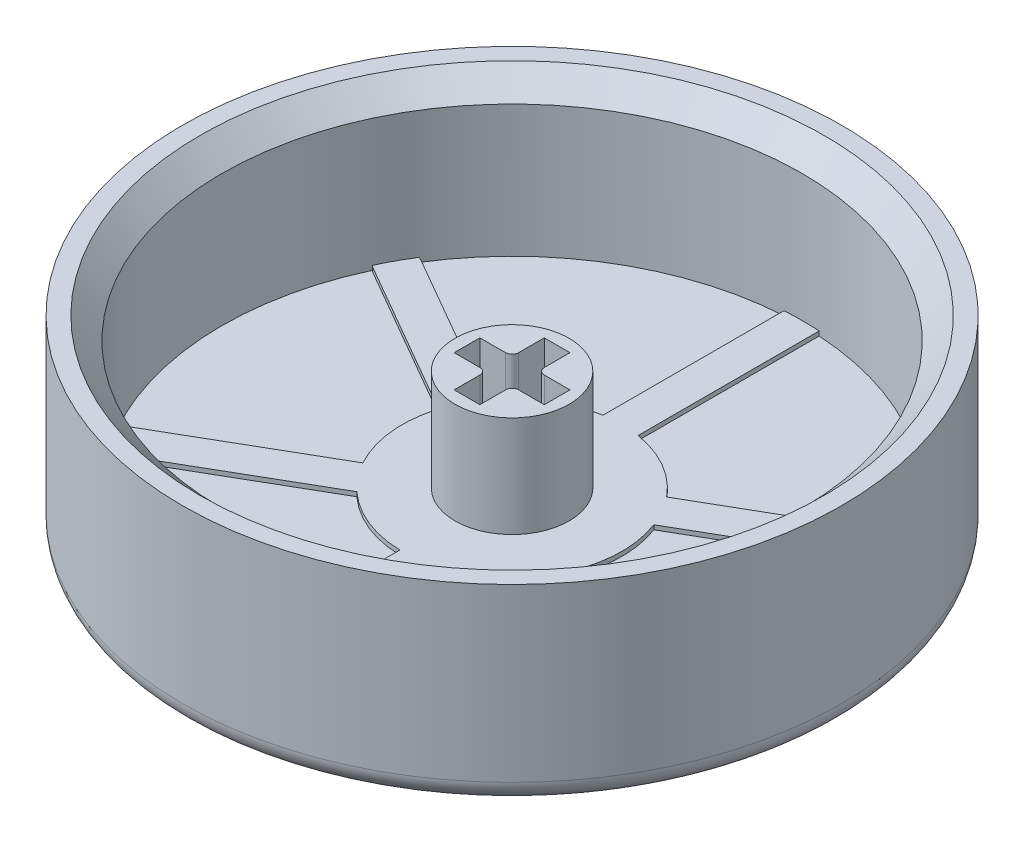
SolidWorks part; units mm, degrees
ref_plane "Front Plane" through (0, 0, 0) normal (0, 0, 1) x (1, 0, 0)
ref_plane "Top Plane" through (0, 0, 0) normal (0, 1, 0) x (1, 0, 0)
ref_plane "Right Plane" through (0, 0, 0) normal (1, 0, 0) x (0, 0, -1)
sketch "Sketch1" plane through (0, 0, 0) normal (0, 1, 0) x (1, 0, 0)
  circle A0 centre (0, 0) radius 15
  dimension "D1" = 30
extrude "button top" add sketch "Sketch1" along normal blind 1.8
sketch "Sketch2" plane through (0, 1.8, 0) normal (0, 1, 0) x (1, 0, 0)
  circle A3 centre (0, 0) radius 15
  circle A4 centre (0, 0) radius 15 construction
  circle A5 centre (0, 0) radius 13.2
  dimension "D1" = 1.8
extrude "button walls" add sketch "Sketch2" along normal blind 7
sketch "Sketch5" plane through (0, 1.8, 0) normal (0, 1, 0) x (1, 0, 0)
  circle A0 centre (0, 0) radius 5
  dimension "D1" = 10
extrude "offset" add sketch "Sketch5" along normal blind 0.2
sketch "Sketch3" plane through (0, 1.8, 0) normal (0, 1, 0) x (1, 0, 0)
  line L0 (0, -2.05) -> (0, 2.05) construction
  line L1 (-2.05, 0) -> (2.05, 0) construction
  line L2 (-0.585, 0.885) -> (-0.585, 2.05)
  line L3 (-0.585, -2.05) -> (0.585, -2.05)
  line L4 (-0.585, -2.05) -> (-0.585, -0.885)
  line L5 (-0.585, 2.05) -> (0.585, 2.05)
  line L6 (0.585, -2.05) -> (0.585, -0.885)
  line L7 (-0.585, -2.05) -> (0.585, 2.05) construction
  line L8 (-0.585, 2.05) -> (0.585, -2.05) construction
  line L9 (-2.05, -0.585) -> (-0.885, -0.585)
  line L10 (-2.05, -0.585) -> (-2.05, 0.585)
  line L11 (-2.05, 0.585) -> (-0.885, 0.585)
  line L12 (2.05, -0.585) -> (2.05, 0.585)
  line L13 (-2.05, -0.585) -> (2.05, 0.585) construction
  line L14 (-2.05, 0.585) -> (2.05, -0.585) construction
  line L15 (0.885, 0.585) -> (2.05, 0.585)
  line L16 (0.585, 0.885) -> (0.585, 2.05)
  line L17 (0.885, -0.585) -> (2.05, -0.585)
  circle A0 centre (0, 0) radius 2.6
  arc A1 (-0.585, -0.885) -> (-0.885, -0.585) centre (-0.885, -0.885) ccw
  arc A2 (0.585, -0.885) -> (0.885, -0.585) centre (0.885, -0.885) cw
  arc A3 (0.885, 0.585) -> (0.585, 0.885) centre (0.885, 0.885) cw
  arc A4 (-0.585, 0.885) -> (-0.885, 0.585) centre (-0.885, 0.885) cw
  point P6 (0, 0)
  point P9 (0, 0)
  point P22 (2.05, 0)
  point P24 (0, 2.05)
  point P29 (0.585, -0.585)
  point P32 (0.585, 0.585)
  dimension "D1" = 5.2
  dimension "D4" = 0.3
  dimension "D2" = 4.1
  dimension "D3" = 1.17
extrude "stem housing" add sketch "Sketch3" along normal blind 4.6 from surface starting at face at (0, 2, 5)
sketch "Sketch4" plane through (0, 1.8, 0) normal (0, 1, 0) x (1, 0, 0)
  line L0 (0, 2.6) -> (0, 13.2) construction
  line L1 (-0.8, 2.6) -> (-0.8, 13.2)
  line L2 (0.8, 2.6) -> (0.8, 13.2)
  line L3 (2.5981, 1.5) -> (11.7779, 6.8) construction
  line L4 (2.1981, 2.1928) -> (11.3779, 7.4928)
  line L5 (2.9981, 0.8072) -> (12.1779, 6.1072)
  line L6 (2.9445, -1.3) -> (12.1244, -6.6) construction
  line L7 (3.3445, -0.6072) -> (12.5244, -5.9072)
  line L8 (2.5445, -1.9928) -> (11.7244, -7.2928)
  line L9 (0.6928, -3) -> (0.6928, -13.6) construction
  line L10 (1.4928, -3) -> (1.4928, -13.6)
  line L11 (-0.1072, -3) -> (-0.1072, -13.6)
  line L12 (-1.9053, -1.9) -> (-11.0851, -7.2) construction
  line L13 (-1.5053, -2.5928) -> (-10.6851, -7.8928)
  line L14 (-2.3053, -1.2072) -> (-11.4851, -6.5072)
  line L15 (-2.2517, 0.9) -> (-11.4315, 6.2) construction
  line L16 (-2.6517, 0.2072) -> (-11.8315, 5.5072)
  line L17 (-1.8517, 1.5928) -> (-11.0315, 6.8928)
  circle A0 centre (0, 0) radius 2.6 construction
  circle A1 centre (0, 0) radius 2.6 construction
  circle A2 centre (0, 0) radius 13.2 construction
  arc A3 (-0.8, 2.6) -> (0.8, 2.6) centre (0, 2.6) ccw
  arc A4 (0.8, 13.2) -> (-0.8, 13.2) centre (0, 13.2) ccw
  arc A5 (2.1981, 2.1928) -> (2.9981, 0.8072) centre (2.5981, 1.5) ccw
  arc A6 (12.1779, 6.1072) -> (11.3779, 7.4928) centre (11.7779, 6.8) ccw
  arc A7 (3.3445, -0.6072) -> (2.5445, -1.9928) centre (2.9445, -1.3) ccw
  arc A8 (11.7244, -7.2928) -> (12.5244, -5.9072) centre (12.1244, -6.6) ccw
  arc A9 (1.4928, -3) -> (-0.1072, -3) centre (0.6928, -3) ccw
  arc A10 (-0.1072, -13.6) -> (1.4928, -13.6) centre (0.6928, -13.6) ccw
  arc A11 (-1.5053, -2.5928) -> (-2.3053, -1.2072) centre (-1.9053, -1.9) ccw
  arc A12 (-11.4851, -6.5072) -> (-10.6851, -7.8928) centre (-11.0851, -7.2) ccw
  arc A13 (-2.6517, 0.2072) -> (-1.8517, 1.5928) centre (-2.2517, 0.9) ccw
  arc A14 (-11.0315, 6.8928) -> (-11.8315, 5.5072) centre (-11.4315, 6.2) ccw
  point P9 (0, 7.9)
  point P18 (7.188, 4.15)
  point P25 (7.5344, -3.95)
  point P32 (0.6928, -8.3)
  point P39 (-6.4952, -4.55)
  point P46 (-6.8416, 3.55)
  point P51 (0.3464, -0.2)
  dimension "D1" = 1.6
  dimension "D2" = 6
extrude "spokes" add sketch "Sketch4" along normal up to surface (0.2 mm away) up to face at (0, 2, 5)
fillet "Fillet1" radius 1 1 edges at (0, 0, 15)
chamfer "Chamfer1" distance 1 angle 45 1 edges at (0, 8.8, 13.2)
